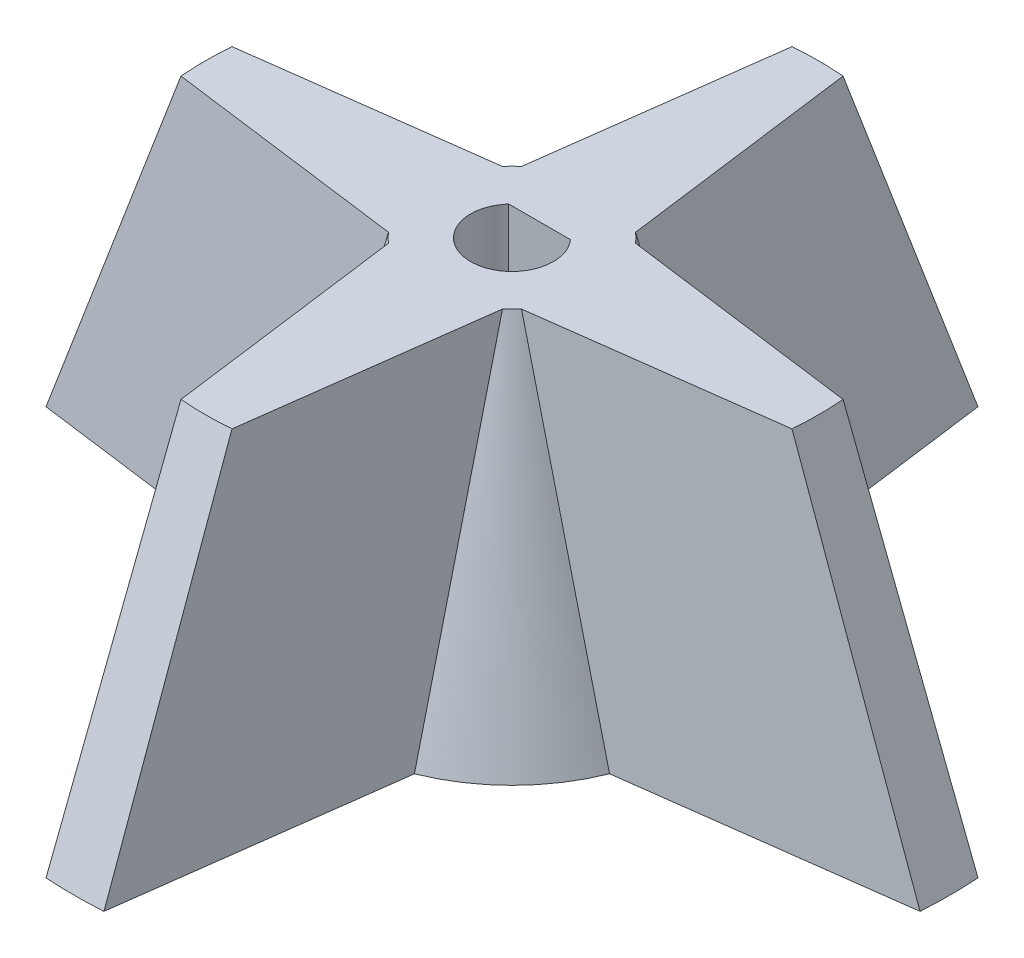
SolidWorks part; units mm, degrees
ref_plane "Front Plane" through (0, 0, 0) normal (0, 0, 1) x (1, 0, 0)
ref_plane "Top Plane" through (0, 0, 0) normal (0, 1, 0) x (1, 0, 0)
ref_plane "Right Plane" through (0, 0, 0) normal (1, 0, 0) x (0, 0, -1)
ref_plane "Plane1" through (0, 25.4, 0) normal (0, 1, 0) x (1, 0, 0)
sketch "Sketch2" plane through (0, 0, 0) normal (0, 1, 0) x (1, 0, 0)
  line L0 (-125.638, 0) -> (125.638, 0) construction
  line L1 (0, -124.5331) -> (0, 124.5331) construction
  line L2 (-4.7185, 11.7909) -> (-2.1, 31.6805)
  line L3 (2.1, 31.6805) -> (4.7185, 11.7909)
  line L4 (11.7909, 4.7185) -> (31.6805, 2.1)
  line L5 (11.7909, -4.7185) -> (31.6805, -2.1)
  line L6 (4.7185, -11.7909) -> (2.1, -31.6805)
  line L7 (-2.1, -31.6805) -> (-4.7185, -11.7909)
  line L8 (-31.6805, -2.1) -> (-11.7909, -4.7185)
  line L9 (-31.6805, 2.1) -> (-11.7909, 4.7185)
  line L10 (-12.9497, 98.3629) -> (-12.0939, 91.8622) construction
  line L12 (0, 88.5098) -> (0, -49911.4902) construction
  line L15 (-2.2361, 2) -> (2.2361, 2)
  arc A2 (4.7185, 11.7909) -> (11.7909, 4.7185) centre (0, 0) cw
  arc A3 (4.7185, -11.7909) -> (11.7909, -4.7185) centre (0, 0) ccw
  arc A4 (-11.7909, -4.7185) -> (-4.7185, -11.7909) centre (0, 0) ccw
  arc A5 (-4.7185, 11.7909) -> (-11.7909, 4.7185) centre (0, 0) ccw
  arc A6 (-2.1, 31.6805) -> (2.1, 31.6805) centre (0, 0) cw
  arc A7 (31.6805, 2.1) -> (31.6805, -2.1) centre (0, 0) cw
  arc A8 (2.1, -31.6805) -> (-2.1, -31.6805) centre (0, 0) cw
  arc A9 (-31.6805, -2.1) -> (-31.6805, 2.1) centre (0, 0) cw
  arc A10 (2.2361, 2) -> (-2.2361, 2) centre (0, 0) cw
  point P28 (-31.75, 0)
  point P29 (31.75, 0)
  point P30 (0, 31.75)
  point P31 (0, -31.75)
  dimension "D5" = 31.75
  dimension "D6" = 12.7
  dimension "D8" = 3
  dimension "D1" = 7.5
  dimension "D7" = 4.2
  dimension "D9" = 2
sketch "Sketch5" plane through (0, 25.4, 0) normal (0, 1, 0) x (1, 0, 0)
  line L0 (-4.1309, 4.8227) -> (-1.85, 22.1479)
  line L1 (1.85, 22.1479) -> (4.1309, 4.8227)
  line L2 (4.8227, 4.1309) -> (22.1479, 1.85)
  line L3 (4.8227, -4.1309) -> (22.1479, -1.85)
  line L4 (4.1309, -4.8227) -> (1.85, -22.1479)
  line L5 (-4.1309, -4.8227) -> (-1.85, -22.1479)
  line L6 (-22.1479, -1.85) -> (-4.8227, -4.1309)
  line L7 (-22.1479, 1.85) -> (-4.8227, 4.1309)
  line L8 (-4.7185, 11.7909) -> (-2.1, 31.6805) construction
  arc A0 (-1.85, 22.1479) -> (1.85, 22.1479) centre (0, 0) cw
  arc A1 (22.1479, 1.85) -> (22.1479, -1.85) centre (0, 0) cw
  arc A2 (1.85, -22.1479) -> (-1.85, -22.1479) centre (0, 0) cw
  arc A3 (-22.1479, -1.85) -> (-22.1479, 1.85) centre (0, 0) cw
  arc A4 (4.1309, 4.8227) -> (4.8227, 4.1309) centre (0, 0) cw
  arc A5 (4.8227, -4.1309) -> (4.1309, -4.8227) centre (0, 0) cw
  arc A6 (-4.1309, -4.8227) -> (-4.8227, -4.1309) centre (0, 0) cw
  arc A7 (-4.8227, 4.1309) -> (-4.1309, 4.8227) centre (0, 0) cw
  point P19 (-22.225, 0)
  point P20 (22.225, 0)
  dimension "D1" = 22.225
  dimension "D2" = 6.35
  dimension "D3" = 3.7
loft "Loft1" add section "Sketch2" section "Sketch5" connector at (31.6805, 0, 2.1) connector at (22.1479, 25.4, 1.85)
extrude "Cut-Extrude1" cut sketch "Sketch2<3>" against normal through all both and the other way through all contours A10 L15 region at (0, 0, 0.296)
sketch "Sketch2<3>" plane through (0, 0, 0) normal (0, 1, 0) x (1, 0, 0) same geometry as "Sketch2"
